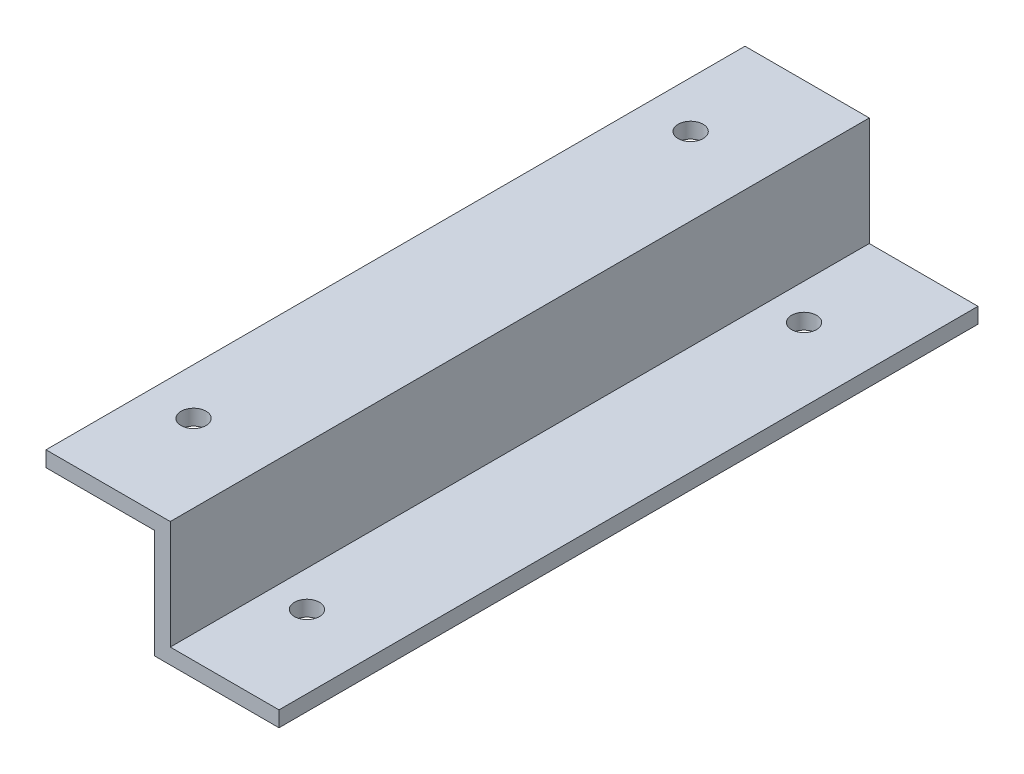
SolidWorks part; units mm, degrees
ref_plane "Front Plane" through (0, 0, 0) normal (0, 0, 1) x (1, 0, 0)
ref_plane "Top Plane" through (0, 0, 0) normal (0, 1, 0) x (1, 0, 0)
ref_plane "Right Plane" through (0, 0, 0) normal (1, 0, 0) x (0, 0, -1)
sketch "Sketch1" plane through (0, 0, 0) normal (0, 0, 1) x (1, 0, 0)
  line L0 (0, -11.1125) -> (0, 11.1125) construction
  line L1 (0, 11.1125) -> (-23.8125, 11.1125) construction
  line L2 (0, -11.1125) -> (23.8125, -11.1125) construction
  line L3 (1.5875, -9.525) -> (23.8125, -9.525) construction
  line L4 (1.5875, -9.525) -> (1.5875, 12.7) construction
  line L5 (1.5875, 12.7) -> (-23.8125, 12.7) construction
  line L6 (-1.5875, -12.7) -> (23.8125, -12.7) construction
  line L7 (-1.5875, -12.7) -> (-1.5875, 9.525) construction
  line L8 (-1.5875, 9.525) -> (-23.8125, 9.525) construction
  line L9 (-23.8125, 12.7) -> (-23.8125, 9.525) construction
  line L10 (23.8125, -9.525) -> (23.8125, -12.7) construction
  point P4 (0, 0)
  dimension "Leg Width" = 25.4
  dimension "Outside Height" = 25.4
  dimension "Wall Thickness" = 3.175
sketch "Sketch2" plane through (0, 0, 0) normal (1, 0, 0) x (0, 0, -1)
  line L0 (71.4375, 0) -> (-71.4375, 0) construction
  line L1 (0, 0) -> (0, 12.7) construction
  line L2 (-71.4375, 0) -> (-71.4375, 12.7) construction
  line L3 (71.4375, 0) -> (71.4375, 12.7) construction
  point P0 (-53.5781, 0)
  point P3 (53.5781, 0)
  point P4 (0, 0)
  dimension "D1" = 107.1562
  dimension "Length" = 142.875
sketch "Sketch3" plane through (0, 0, 0) normal (0, 0, 1) x (1, 0, 0)
  line L0 (23.8125, -9.525) -> (23.8125, -12.7) construction
  line L1 (1.5875, -9.525) -> (23.8125, -9.525) construction
  line L2 (-1.5875, -12.7) -> (23.8125, -12.7) construction
  line L3 (-1.5875, -12.7) -> (-1.5875, 9.525) construction
  line L4 (1.5875, -9.525) -> (1.5875, 12.7) construction
  line L5 (1.5875, 12.7) -> (-23.8125, 12.7) construction
  line L6 (-23.8125, 12.7) -> (-23.8125, 9.525) construction
  line L7 (-1.5875, 9.525) -> (-23.8125, 9.525) construction
  line L8 (23.8125, -9.525) -> (23.8125, -12.7)
  line L9 (1.5875, -9.525) -> (23.8125, -9.525)
  line L10 (-1.5875, -12.7) -> (23.8125, -12.7)
  line L11 (-1.5875, -12.7) -> (-1.5875, 9.525)
  line L12 (1.5875, -9.525) -> (1.5875, 12.7)
  line L13 (1.5875, 12.7) -> (-23.8125, 12.7)
  line L14 (-23.8125, 12.7) -> (-23.8125, 9.525)
  line L15 (-1.5875, 9.525) -> (-23.8125, 9.525)
extrude "Boss-Extrude1" add sketch "Sketch3" along normal up to vertex (71.4375 mm away) and the other way up to vertex (71.4375 mm away) up to point (0, 0, 71.4375) other way up to point (0, 0, -71.4375)
hole_wizard "#10 Clearance Hole1" positions "Sketch4" profile "Sketch5" hole size "#10" standard "ANSI Inch" end condition through all
sketch "Sketch4" plane through (0, 12.7, 0) normal (0, 1, 0) x (1, 0, 0)
  point P0 (-14.2875, -50.8)
  point P3 (-14.2875, 50.8)
sketch "Sketch5" plane through (-14.2875, 12.7, 50.8) normal (1, 0, 0) x (0, 0, 1)
  line L0 (0, 0) -> (0, 25.4)
  line L1 (0, 25.4) -> (2.5527, 25.4)
  line L2 (2.5527, 25.4) -> (2.5527, 0)
  line L5 (2.5527, 0) -> (0, 0)
  line L11 (0, -6.35) -> (0, 107.95) construction
  dimension "Thru Hole Dia." = 5.1054
  dimension "Thru Hole Depth" = 25.4
sketch "Sketch7" plane through (0, -9.525, 0) normal (0, 1, 0) x (1, 0, 0)
  line L0 (-14.2875, -50.8) -> (8.89, -50.8) construction
  line L1 (8.89, -50.8) -> (8.89, 50.7997) construction
hole_wizard "#10 Clearance Hole2" positions "Sketch8" profile "Sketch9" hole size "#10" standard "ANSI Inch" end condition through all
sketch "Sketch8" plane through (0, -9.525, 0) normal (0, 1, 0) x (1, 0, 0)
  point P0 (8.89, -50.8)
  point P3 (8.89, 50.7997)
sketch "Sketch9" plane through (8.89, -9.525, 50.8) normal (1, 0, 0) x (0, 0, 1)
  line L0 (0, 0) -> (0, 3.175)
  line L1 (0, 3.175) -> (2.5527, 3.175)
  line L2 (2.5527, 3.175) -> (2.5527, 0)
  line L5 (2.5527, 0) -> (0, 0)
  line L11 (0, -6.35) -> (0, 107.95) construction
  dimension "Thru Hole Dia." = 5.1054
  dimension "Thru Hole Depth" = 3.175
equation "\"D1@Sketch2\"=\"Length@Sketch2\"*0.75"
